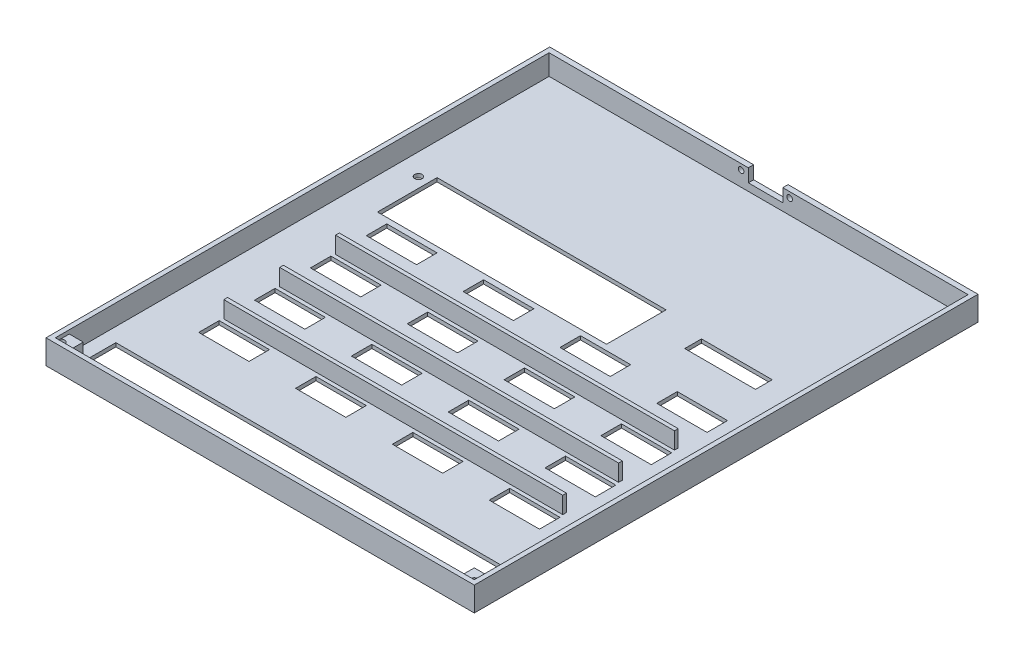
SolidWorks part; units mm, degrees
ref_plane "Plan de face" through (0, 0, 0) normal (0, 0, 1) x (1, 0, 0)
ref_plane "Plan de dessus" through (0, 0, 0) normal (0, 1, 0) x (1, 0, 0)
ref_plane "Plan de droite" through (0, 0, 0) normal (1, 0, 0) x (0, 0, -1)
sketch "Esquisse3" plane through (0, 0, 0) normal (0, 1, 0) x (1, 0, 0)
  line L1 (112.5, -95) -> (-112.5, -95)
  line L2 (112.5, -95) -> (112.5, 95)
  line L3 (112.5, 95) -> (-112.5, 95)
  line L4 (-112.5, -95) -> (-112.5, 95)
  line L5 (112.5, -95) -> (-112.5, 95) construction
  line L6 (112.5, 95) -> (-112.5, -95) construction
  line L7 (-105, -90) -> (104.5, -90)
  line L8 (-105, -90) -> (-105, -70)
  line L9 (-105, -70) -> (104.5, -70)
  line L10 (-95.5, 63) -> (27.5, 63)
  line L11 (-95.5, 63) -> (-95.5, 93)
  line L12 (-95.5, 93) -> (27.5, 93)
  line L13 (27.5, 63) -> (27.5, 93)
  line L14 (104.5, -90) -> (104.5, -70)
  point P0 (0, 0)
  dimension "D1" = 190
  dimension "D2" = 225
  dimension "D3" = 2
  dimension "D4" = 5
  dimension "D5" = 30
  dimension "D6" = 8
  dimension "D7" = 85
  dimension "D8" = 17
  dimension "D9" = 20
  dimension "D10" = 7.5
extrude "Bloc coque" add sketch "Esquisse3" along normal blind 16
sketch "Esquisse5" plane through (0, 16, 0) normal (0, 1, 0) x (1, 0, 0)
  line L0 (-112.5, 95) -> (-112.5, -95) construction
  line L1 (-87.5, 58) -> (-60.5, 58)
  line L2 (-87.5, 58) -> (-87.5, 47)
  line L3 (-87.5, 47) -> (-60.5, 47)
  line L4 (-60.5, 58) -> (-60.5, 47)
  line L5 (-8.5, 58) -> (-8.5, 47)
  line L6 (-35.5, 58) -> (-8.5, 58)
  line L7 (-35.5, 58) -> (-35.5, 47)
  line L8 (-35.5, 47) -> (-8.5, 47)
  line L9 (43.5, 58) -> (43.5, 47)
  line L10 (16.5, 58) -> (43.5, 58)
  line L11 (16.5, 58) -> (16.5, 47)
  line L12 (16.5, 47) -> (43.5, 47)
  line L13 (95.5, 58) -> (95.5, 47)
  line L14 (68.5, 58) -> (95.5, 58)
  line L15 (68.5, 58) -> (68.5, 47)
  line L16 (68.5, 47) -> (95.5, 47)
  line L17 (-8.5, 28) -> (-8.5, 17)
  line L18 (-35.5, 28) -> (-8.5, 28)
  line L19 (-35.5, 28) -> (-35.5, 17)
  line L20 (-35.5, 17) -> (-8.5, 17)
  line L21 (43.5, 28) -> (43.5, 17)
  line L22 (16.5, 28) -> (43.5, 28)
  line L23 (16.5, 28) -> (16.5, 17)
  line L24 (16.5, 17) -> (43.5, 17)
  line L25 (95.5, 28) -> (95.5, 17)
  line L26 (68.5, 28) -> (95.5, 28)
  line L27 (68.5, 28) -> (68.5, 17)
  line L28 (68.5, 17) -> (95.5, 17)
  line L29 (-8.5, -2) -> (-8.5, -13)
  line L30 (-35.5, -2) -> (-8.5, -2)
  line L31 (-35.5, -2) -> (-35.5, -13)
  line L32 (-35.5, -13) -> (-8.5, -13)
  line L33 (43.5, -2) -> (43.5, -13)
  line L34 (16.5, -2) -> (43.5, -2)
  line L35 (16.5, -2) -> (16.5, -13)
  line L36 (16.5, -13) -> (43.5, -13)
  line L37 (95.5, -2) -> (95.5, -13)
  line L38 (68.5, -2) -> (95.5, -2)
  line L39 (68.5, -2) -> (68.5, -13)
  line L40 (68.5, -13) -> (95.5, -13)
  line L41 (-8.5, -32) -> (-8.5, -43)
  line L42 (-35.5, -32) -> (-8.5, -32)
  line L43 (-35.5, -32) -> (-35.5, -43)
  line L44 (-35.5, -43) -> (-8.5, -43)
  line L45 (43.5, -32) -> (43.5, -43)
  line L46 (16.5, -32) -> (43.5, -32)
  line L47 (16.5, -32) -> (16.5, -43)
  line L48 (16.5, -43) -> (43.5, -43)
  line L49 (95.5, -32) -> (95.5, -43)
  line L50 (68.5, -32) -> (95.5, -32)
  line L51 (68.5, -32) -> (68.5, -43)
  line L52 (68.5, -43) -> (95.5, -43)
  line L53 (-60.5, 28) -> (-60.5, 17)
  line L54 (-87.5, 28) -> (-60.5, 28)
  line L55 (-87.5, 28) -> (-87.5, 17)
  line L56 (-87.5, 17) -> (-60.5, 17)
  line L57 (-60.5, -2) -> (-60.5, -13)
  line L58 (-87.5, -2) -> (-60.5, -2)
  line L59 (-87.5, -2) -> (-87.5, -13)
  line L60 (-87.5, -13) -> (-60.5, -13)
  line L61 (-60.5, -32) -> (-60.5, -43)
  line L62 (-87.5, -32) -> (-60.5, -32)
  line L63 (-87.5, -32) -> (-87.5, -43)
  line L64 (-87.5, -43) -> (-60.5, -43)
  line L66 (-112.5, -95) -> (112.5, -95) construction
  dimension "D1" = 27
  dimension "D2" = 25
  dimension "D5" = 52
  dimension "D6" = 25
  dimension "D7" = 19
  dimension "D8" = 11
  dimension "D3" = 4
  dimension "D4" = 4
extrude "Trou cartouche" cut sketch "Esquisse5" against normal through all
shell "Coque5" thickness 2 removed face at (30, 16, 7.5)
sketch "Esquisse6" plane through (0, 16, 0) normal (0, 1, 0) x (1, 0, 0)
  line L0 (-110.5, 93) -> (-110.5, -93) construction
  line L1 (-110.5, -90.5) -> (27.5, -90.5)
  line L2 (-110.5, -90.5) -> (-110.5, 93)
  line L3 (-110.5, 93) -> (27.5, 93)
  line L4 (27.5, -90.5) -> (27.5, 93)
extrude "Logement carte" cut sketch "Esquisse6" against normal blind 6
sketch "Esquisse10" plane through (0, 0, 0) normal (0, -1, 0) x (-1, 0, 0)
  circle A4 centre (-104, 88.5) radius 2
  circle A5 centre (101, 88.5) radius 2
  circle A7 centre (-104, -84.5) radius 2
  dimension "D1" = 4
  dimension "D3" = 4
  dimension "D2" = 4
extrude "Enlèv. mat.-Extru.2" cut sketch "Esquisse10" against normal blind 15
sketch "Esquisse12" plane through (0, 16, 0) normal (0, 1, 0) x (1, 0, 0)
  line L0 (27.5, 93) -> (-110.5, 93) construction
  line L1 (10.5, 93) -> (110.5, 93)
  line L2 (10.5, 93) -> (10.5, -93)
  line L3 (10.5, -93) -> (110.5, -93)
  line L4 (110.5, 93) -> (110.5, -93)
  dimension "D1" = 100
extrude "Enlèv. mat.-Extru.4" cut sketch "Esquisse12" against normal blind 6
sketch "Esquisse13" plane through (0, 0, -63) normal (0, 0, -1) x (-1, 0, 0)
  line L1 (95.5, 0) -> (-27.5, 0)
  line L2 (95.5, 0) -> (95.5, 10)
  line L3 (95.5, 10) -> (-27.5, 10)
  line L4 (-27.5, 0) -> (-27.5, 10)
extrude "Enlèv. mat.-Extru.5" cut sketch "Esquisse13" against normal blind 2
sketch "Esquisse14" plane through (0, 10, 0) normal (0, 1, 0) x (1, 0, 0)
  line L1 (-95.5, 61) -> (104.5, 61)
  line L2 (-95.5, 61) -> (-95.5, -47.9751)
  line L3 (-95.5, -47.9751) -> (104.5, -47.9751)
  line L4 (104.5, 61) -> (104.5, -47.9751)
  dimension "D1" = 200
extrude "Enlèv. mat.-Extru.6" cut sketch "Esquisse14" against normal blind 8
sketch "Esquisse16" plane through (0, 0, 0) normal (0, -1, 0) x (1, 0, 0)
  line L0 (112.5, -95) -> (-112.5, -95) construction
  line L1 (50.5, -80) -> (88.5, -80)
  line L2 (50.5, -80) -> (50.5, -89)
  line L3 (50.5, -89) -> (88.5, -89)
  line L4 (88.5, -80) -> (88.5, -89)
  line L5 (112.5, 95) -> (112.5, -95) construction
  dimension "D1" = 6
  dimension "D2" = 24
  dimension "D3" = 62
  dimension "D4" = 15
extrude "Enlèv. mat.-Extru.7" cut sketch "Esquisse16" against normal blind 10
sketch "Esquisse17" plane through (0, 0, 0) normal (0, -1, 0) x (1, 0, 0)
  line L1 (-112.5, 95) -> (112.5, 95)
  line L2 (-112.5, 95) -> (-112.5, -95)
  line L3 (-112.5, -95) -> (112.5, -95)
  line L4 (112.5, 95) -> (112.5, -95)
  line L5 (-115, 97.5) -> (115, 97.5)
  line L6 (-115, 97.5) -> (-115, -97.5)
  line L7 (-115, -97.5) -> (115, -97.5)
  line L8 (115, 97.5) -> (115, -97.5)
  dimension "D1" = 2.5
  dimension "D2" = 2.5
  dimension "D3" = 2.5
  dimension "D4" = 2.5
extrude "Boss.-Extru.2" add sketch "Esquisse17" against normal blind 13 separate body
sketch "Esquisse18" plane through (0, 13, 0) normal (0, 1, 0) x (1, 0, 0)
  line L0 (115, 97.5) -> (115, -97.5) construction
  line L1 (-115, 97.5) -> (115, 97.5)
  line L2 (-115, 97.5) -> (-115, 93)
  line L3 (-115, 93) -> (115, 93)
  line L4 (115, 97.5) -> (115, 93)
  dimension "D1" = 4.5
extrude "Enlèv. mat.-Extru.8" cut sketch "Esquisse18" against normal through all
sketch "Esquisse20" plane through (0, 0, 0) normal (0, -1, 0) x (1, 0, 0)
  line L0 (115, -93) -> (115, 97.5) construction
  line L1 (-115, -93) -> (115, -93)
  line L2 (-115, -93) -> (-115, -173)
  line L3 (-115, -173) -> (115, -173)
  line L4 (115, -93) -> (115, -173)
  dimension "D1" = 80
  dimension "D2" = 0
extrude "Boss.-Extru.3" add sketch "Esquisse20" against normal blind 13
sketch "Esquisse21" plane through (0, 13, 0) normal (0, 1, 0) x (1, 0, 0)
  line L7 (112.5, 95) -> (-112.5, 95)
  line L8 (112.5, 95) -> (112.5, 170.1522)
  line L9 (112.5, 170.1522) -> (-112.5, 170.1522)
  line L10 (-112.5, 95) -> (-112.5, 170.1522)
  dimension "D1" = 225
  dimension "D2" = 75.1522
extrude "Enlèv. mat.-Extru.9" cut sketch "Esquisse21" against normal blind 7
sketch "Esquisse25" plane through (0, 0, -173) normal (0, 0, -1) x (-1, 0, 0)
  line L0 (115, 0) -> (-115, 0) construction
  line L3 (5.5, 6) -> (-13, 6)
  line L4 (5.5, 6) -> (5.5, 15.5)
  line L5 (5.5, 15.5) -> (-13, 15.5)
  line L6 (-13, 6) -> (-13, 15.5)
  line L7 (-115, 13) -> (-115, 0) construction
  dimension "D1" = 18.5
  dimension "D2" = 9.5
  dimension "D3" = 6
  dimension "D4" = 102
extrude "Enlèv. mat.-Extru.11" cut sketch "Esquisse25" against normal blind 10
sketch "Esquisse29" plane through (0, 0, -170.1522) normal (0, 0, 1) x (1, 0, 0)
  line L0 (-107, 10) -> (106.5, 10) construction
  circle A1 centre (16.6896, 10) radius 1.5
  circle A3 centre (-9.392, 10) radius 1.5
  dimension "D1" = 3
  dimension "D2" = 3
extrude "Enlèv. mat.-Extru.14" cut sketch "Esquisse29" against normal blind 6
sketch "Esquisse36" plane through (0, 16, 0) normal (0, 1, 0) x (1, 0, 0)
  line L0 (112.5, 170.1522) -> (13, 170.1522) construction
  line L1 (-112.5, -95) -> (112.5117, -95)
  line L2 (-112.5, -95) -> (-112.5, 170.1522)
  line L3 (-112.5, 170.1522) -> (112.5117, 170.1522)
  line L4 (112.5117, -95) -> (112.5117, 170.1522)
  dimension "D1" = 0
extrude "Enlèv. mat.-Extru.18" cut sketch "Esquisse36" against normal blind 14
sketch "Esquisse30" plane through (0, 0, 0) normal (0, -1, 0) x (1, 0, 0)
  line L0 (0, -218.2764) -> (0, 110.805) construction
  line L1 (115, 97.5) -> (105, 97.5)
  line L2 (115, 97.5) -> (115, 87.5)
  line L3 (115, 87.5) -> (105, 87.5)
  line L4 (105, 97.5) -> (105, 87.5)
  line L5 (-115, 97.5) -> (-115, 87.5)
  line L6 (-115, 97.5) -> (-105, 97.5)
  line L7 (-105, 97.5) -> (-105, 87.5)
  line L8 (-115, 87.5) -> (-105, 87.5)
  dimension "D1" = 10
  dimension "D2" = 10
extrude "Boss.-Extru.4" add sketch "Esquisse30" against normal blind 11
sketch "Esquisse33" plane through (0, 11, 0) normal (0, 1, 0) x (1, 0, 0)
  line L2 (0, 208.9911) -> (0, -200.4124) construction
  line L3 (115, -97.5) -> (-115, -97.5) construction
  line L4 (-115, -97.5) -> (-115, 173) construction
  circle A2 centre (-111, -93.5) radius 2
  circle A3 centre (111, -93.5) radius 2
  point P11 (0, 0)
  dimension "D1" = 4
  dimension "D2" = 4
  dimension "D3" = 4
extrude "Enlèv. mat.-Extru.16" cut sketch "Esquisse33" against normal through all
sketch "Esquisse37" plane through (0, 2, 0) normal (0, 1, 0) x (1, 0, 0)
  line L0 (-87.5, -32) -> (-60.5, -32) construction
  line L1 (-87, -28) -> (95, -28)
  line L2 (-87, -28) -> (-87, -30)
  line L3 (-87, -30) -> (95, -30)
  line L4 (95, -28) -> (95, -30)
  line L5 (-115, -97.5) -> (-115, 173) construction
  line L6 (115, 173) -> (115, -97.5) construction
  line L7 (-35.5, -2) -> (-8.5, -2) construction
  line L8 (-87, 2) -> (95, 2)
  line L9 (-87, 2) -> (-87, 0)
  line L10 (-87, 0) -> (95, 0)
  line L11 (95, 2) -> (95, 0)
  line L12 (-87.5, 28) -> (-60.5, 28) construction
  line L13 (-87, 30) -> (95, 30)
  line L14 (-87, 30) -> (-87, 32)
  line L15 (-87, 32) -> (95, 32)
  line L16 (95, 30) -> (95, 32)
  dimension "D1" = 2
  dimension "D2" = 2
  dimension "D3" = 28
  dimension "D4" = 20
  dimension "D5" = 2
  dimension "D6" = 2
  dimension "D7" = 2
  dimension "D8" = 2
extrude "Boss.-Extru.6" add sketch "Esquisse37" along normal blind 9
